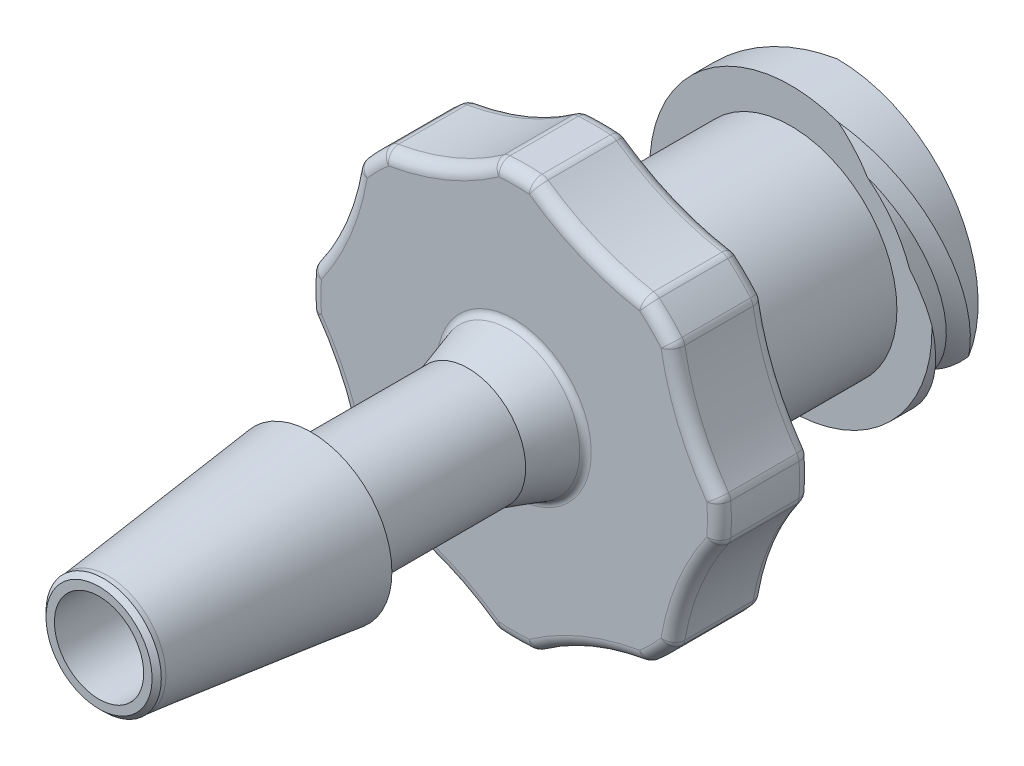
SolidWorks part; units mm, degrees
ref_plane "Front Plane" through (0, 0, 0) normal (0, 0, 1) x (1, 0, 0)
ref_plane "Top Plane" through (0, 0, 0) normal (0, 1, 0) x (1, 0, 0)
ref_plane "Right Plane" through (0, 0, 0) normal (1, 0, 0) x (0, 0, -1)
sketch "Sketch1" plane through (0, 0, 0) normal (1, 0, 0) x (0, 0, -1)
  line L0 (-10.16, 0) -> (10.16, 0) construction
  line L1 (0, -5.6515) -> (0, 5.6515) construction
  line L2 (-9.906, -1.5875) -> (-9.906, 1.5875) construction
  line L3 (0, -2.159) -> (0, 2.159) construction
  line L4 (-10.16, -2.2225) -> (-10.16, 2.2225) construction
  line L5 (-10.16, -1.1176) -> (-10.16, 1.1176) construction
  point P8 (0, 0)
  point P11 (-9.906, 0)
  point P13 (0, 0)
  point P20 (-10.16, 2.2225)
  point P21 (-10.16, 1.1176)
  point P22 (-10.16, -2.2225)
  point P23 (-10.16, -1.1176)
  dimension "Length" = 20.32
  dimension "OD" = 11.303
  dimension "D2" = 0.254
  dimension "For Tube ID" = 3.175
  dimension "Barb ID" = 2.2352
  dimension "Barb OD" = 4.445
  dimension "ID" = 4.318
sketch "Sketch2" plane through (0, 0, 0) normal (1, 0, 0) x (0, 0, -1)
  line L0 (1.27, 5.6515) -> (3.81, 5.6515)
  line L1 (3.81, 5.6515) -> (3.81, 0)
  line L2 (-10.16, 0) -> (10.16, 0) construction
  line L3 (3.81, 0) -> (1.27, 0)
  line L4 (1.27, 0) -> (1.27, 5.6515) construction
  line L5 (-9.906, 1.5875) -> (-10.16, 1.5875)
  line L6 (-10.16, 1.5875) -> (-10.16, 0)
  line L7 (-10.16, 0) -> (-9.906, 0)
  line L8 (-9.906, 0) -> (-9.906, 1.5875) construction
  line L9 (-9.906, 1.5875) -> (-4.318, 1.5875) construction
  line L10 (-4.318, 1.5875) -> (1.27, 1.5875) construction
  line L11 (-9.906, 1.5875) -> (-4.318, 2.2225)
  line L12 (-4.318, 2.2225) -> (-4.318, 1.5875)
  line L13 (-4.318, 1.5875) -> (0, 1.5875)
  line L14 (0, 1.5875) -> (1.27, 1.9844)
  line L15 (-9.906, 0) -> (1.27, 0)
  line L16 (1.27, 1.9844) -> (1.27, 5.6515)
  dimension "D1" = 2.54
  dimension "D3" = 1.27
  dimension "D4" = 0.3969
  dimension "D5" = 6.35
revolve "Revolve1" add sketch "Sketch2" angle 360 about L0
chamfer "Chamfer1" distance 0.127 angle 45 1 edges at (1.5875, 0, 10.16)
sketch "Sketch4" plane through (0, 0, 0) normal (1, 0, 0) x (0, 0, -1)
  line L1 (10.16, 0) -> (3.81, 0)
  line L3 (3.81, 2.921) -> (3.81, 0)
  line L5 (3.81, -5.6515) -> (3.81, 5.6515) construction
  line L8 (3.81, 2.921) -> (8.89, 2.921)
  line L9 (8.89, 2.921) -> (8.89, 3.8862)
  line L11 (8.89, 3.8862) -> (10.16, 3.8862)
  line L12 (10.16, 3.8862) -> (10.16, 0)
  dimension "D2" = 3.8862
  dimension "D3" = 1.27
  dimension "D10" = 2.921
revolve "Revolve2" add sketch "Sketch4" angle 360 about L0
sketch "Sketch8" plane through (0, 0, 0) normal (0, 0, 1) x (1, 0, 0)
  line L0 (-4.724, -11.4047) -> (4.724, 11.4047) construction
  line L2 (0, -5.6515) -> (0, 5.6515) construction
  circle A0 centre (4.724, 11.4047) radius 7.1374
  point P3 (0, 0)
  dimension "D3" = 14.2748
  dimension "D1" = 24.6888
  dimension "D2" = 22.5
extrude "Cut-Extrude2" cut sketch "Sketch8" against normal through all both and the other way through all
pattern_circular "CirPattern2" count 8 over 360 about axis through (0, 0, 10.16) along (0, 0, -1) of "Cut-Extrude2"
fillet "Fillet2" radius 0.3302 48 edges at (3.9962, 3.9962, -1.27) (5.6515, 0, -1.27) (5.6262, 0.5347, -2.54) (4.3564, 3.6002, -2.54) (4.8106, 1.9926, -1.27) (4.8106, -1.9926, -1.27) (4.3564, -3.6002, -2.54) (5.6262, -0.5347, -2.54) (3.9962, -3.9962, -1.27) (1.9926, -4.8106, -1.27) (0.5347, -5.6262, -2.54) (3.6002, -4.3564, -2.54) (0, -5.6515, -1.27) (-1.9926, -4.8106, -1.27) (-3.6002, -4.3564, -2.54) (-0.5347, -5.6262, -2.54) (-3.9962, -3.9962, -1.27) (-4.8106, -1.9926, -1.27) (-5.6262, -0.5347, -2.54) (-4.3564, -3.6002, -2.54) (-5.6515, 0, -1.27) (-3.9962, 3.9962, -1.27) (-4.3564, 3.6002, -2.54) (-5.6262, 0.5347, -2.54) (-4.8106, 1.9926, -1.27) (0, 5.6515, -1.27) (3.6002, 4.3564, -2.54) (1.9926, 4.8106, -1.27) (0.5347, 5.6262, -2.54) (-0.5347, 5.6262, -2.54) (-3.6002, 4.3564, -2.54) (-1.9926, 4.8106, -1.27) (3.9962, 3.9962, -3.81) (5.6515, 0, -3.81) (4.8106, 1.9926, -3.81) (4.8106, -1.9926, -3.81) (3.9962, -3.9962, -3.81) (1.9926, -4.8106, -3.81) (0, -5.6515, -3.81) (-1.9926, -4.8106, -3.81) (-3.9962, -3.9962, -3.81) (-4.8106, -1.9926, -3.81) (-5.6515, 0, -3.81) (-3.9962, 3.9962, -3.81) (-4.8106, 1.9926, -3.81) (0, 5.6515, -3.81) (1.9926, 4.8106, -3.81) (-1.9926, 4.8106, -3.81)
sketch "Sketch9" plane through (0, 0, 0) normal (1, 0, 0) x (0, 0, -1)
  line L0 (10.16, 2.159) -> (10.16, -2.159) construction
  line L1 (2.54, 5.6515) -> (2.54, 2.026) construction
  line L2 (1.27, 5.6515) -> (3.81, 5.6515) construction
  line L3 (2.54, 2.026) -> (10.16, 2.159)
  line L4 (-10.16, -2.2225) -> (-10.16, 2.2225) construction
  line L5 (2.54, 2.026) -> (2.54, 1.1176)
  line L6 (2.54, 1.1176) -> (-10.16, 1.2284)
  line L7 (-10.16, 1.5875) -> (-10.16, 0) construction
  line L8 (-10.16, 1.2284) -> (-10.16, 0)
  line L9 (-10.16, 0) -> (10.16, 0)
  line L10 (10.16, 0) -> (10.16, 2.159)
  point P4 (10.16, 0)
  dimension "D1" = 0.5
  dimension "D2" = 1
revolve "Cut-Revolve2" cut sketch "Sketch9" angle 360 about L0
fillet "Fillet3" radius 0.7937 1 edges at (2.921, 0, -3.81)
fillet "Fillet4" radius 0.1905 1 edges at (1.9844, 0, -1.27)
sketch "Sketch10" plane through (0, 0, -10.16) normal (0, 0, 1) x (1, 0, 0)
  circle A1 centre (0, 0) radius 3.8862
  circle A2 centre (0, 0) radius 3.8862 construction
curve "Helix/Spiral1" pitch 5 height 3.175 radius 3.8862 centre (0, 0, -10.16) axis (0, 0, 1) start towards (0, 1, 0)
sketch "Sketch11" plane through (0, 0, 0) normal (1, 0, 0) x (0, 0, -1)
  line L0 (10.4059, 3.4604) -> (10.8694, 3.4604)
  line L1 (10.8694, 3.4604) -> (11.1153, 3.8862)
  line L2 (11.1153, 3.8862) -> (10.16, 3.8862) construction
  line L3 (10.16, 3.8862) -> (10.4059, 3.4604)
  line L4 (10.16, 3.8862) -> (10.1307, 3.937)
  line L6 (10.1307, 3.937) -> (11.1446, 3.937)
  line L7 (11.1446, 3.937) -> (11.1153, 3.8862)
  dimension "D1" = 60
  dimension "D2" = 0.4258
  dimension "D3" = 0.4766
  dimension "D4" = 0.9553
sweep "Cut-Sweep1" cut profiles "Sketch11" path "Helix/Spiral1" align with end faces yes
pattern_circular "CirPattern3" count 2 over 360 about axis through (0, 0, 10.16) along (0, 0, -1) of "Cut-Sweep1" reverse direction yes
equation "\"D3@Sketch2\" = ( \"Length@Sketch1\" - .4 ) * .125"
equation "\"D1@Fillet4\"=\"D3@Sketch2\"*.15"
